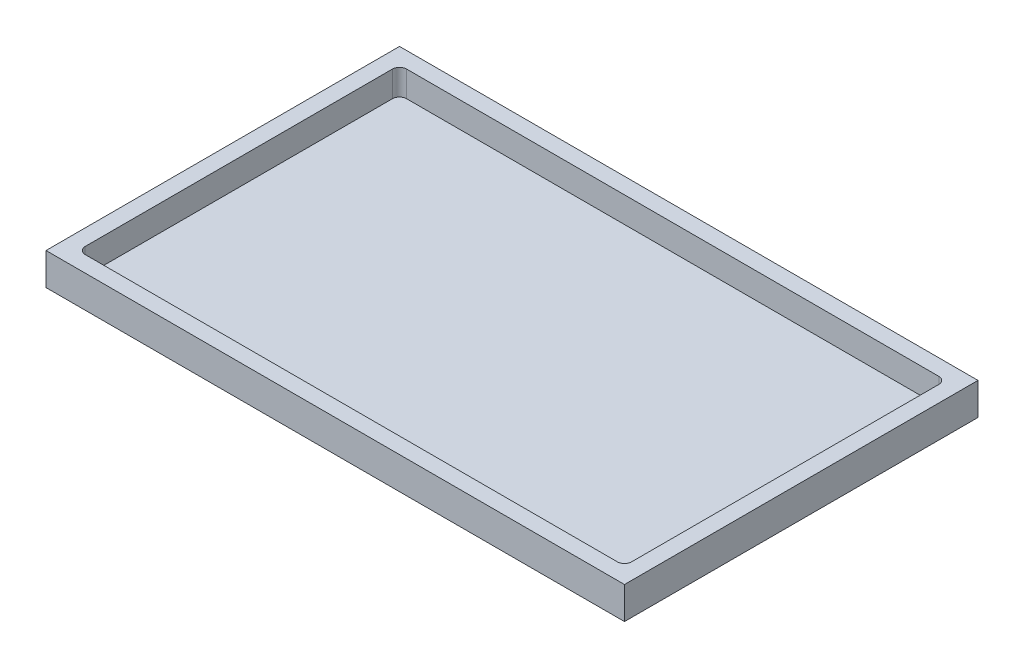
SolidWorks part; units mm, degrees
ref_plane "Ebene vorne" through (0, 0, 0) normal (0, 0, 1) x (1, 0, 0)
ref_plane "Ebene oben" through (0, 0, 0) normal (0, 1, 0) x (1, 0, 0)
ref_plane "Ebene rechts" through (0, 0, 0) normal (1, 0, 0) x (0, 0, -1)
sketch "Sketch1" plane through (0, 0, 0) normal (0, 1, 0) x (1, 0, 0)
  line L1 (-450, -275) -> (450, -275)
  line L2 (-450, -275) -> (-450, 275)
  line L3 (-450, 275) -> (450, 275)
  line L4 (450, -275) -> (450, 275)
  line L5 (-450, -275) -> (450, 275) construction
  line L6 (-450, 275) -> (450, -275) construction
  point P0 (0, 0)
  dimension "D1" = 550
  dimension "D2" = 900
extrude "Boss-Extrude1" add sketch "Sketch1" along normal blind 50
sketch "Sketch2" plane through (0, 50, 0) normal (0, 1, 0) x (1, 0, 0)
  line L1 (-425, -250) -> (425, -250)
  line L2 (-425, -250) -> (-425, 250)
  line L3 (-425, 250) -> (425, 250)
  line L4 (425, -250) -> (425, 250)
  line L5 (-425, -250) -> (425, 250) construction
  line L6 (-425, 250) -> (425, -250) construction
  point P0 (0, 0)
  dimension "D1" = 500
  dimension "D2" = 850
extrude "Cut-Extrude1" cut sketch "Sketch2" against normal blind 40 contours L2 L3 L4 L1
sketch "Sketch3" plane through (0, 10, 0) normal (0, 1, 0) x (1, 0, 0)
  line L0 (-425, 250) -> (-395, 250)
  line L1 (-425, 250) -> (425, 250) construction
  line L2 (-425, 250) -> (-425, 220)
  line L3 (-425, -250) -> (-425, 250) construction
  line L4 (-425, 220) -> (-395, 250)
extrude "Boss-Extrude2" [suppressed] add sketch "Sketch3" along normal blind 34 contours L4 L0 L2
mirror "Mirror1" [suppressed] about plane through (0, 0, 0) normal (0, 0, 1)
mirror "Mirror2" [suppressed] about plane through (0, 0, 0) normal (1, 0, 0)
fillet "Fillet1" radius 11 4 edges at (-425, 30, 250) (-425, 30, -250) (425, 30, -250) (425, 30, 250)
